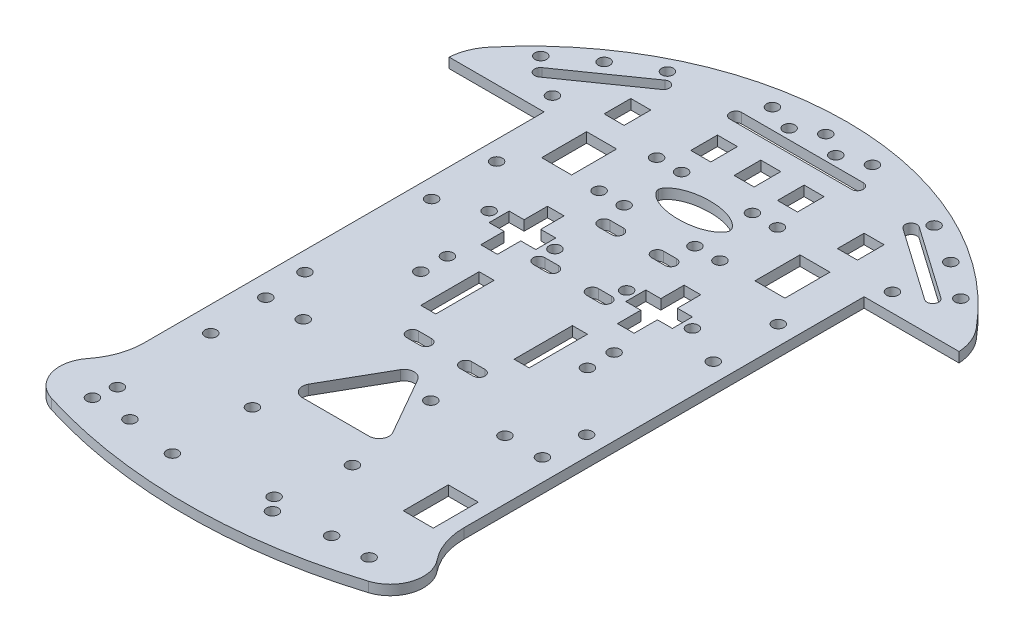
SolidWorks part; units mm, degrees
ref_plane "Front Plane" through (0, 0, 0) normal (0, 0, 1) x (1, 0, 0)
ref_plane "Top Plane" through (0, 0, 0) normal (0, 1, 0) x (1, 0, 0)
ref_plane "Right Plane" through (0, 0, 0) normal (1, 0, 0) x (0, 0, -1)
ref_plane "Plane4" through (0, -1.5, 0) normal (0, -1, 0) x (1, 0, 0)
sketch "Sketch1" plane through (0, -1.5, 0) normal (0, -1, 0) x (1, 0, 0)
  line L0 (6, 21.75) -> (10, 21.75)
  line L1 (10, 18.25) -> (6, 18.25)
  line L2 (-10, 41.25) -> (-6, 41.25)
  line L3 (-6, 37.75) -> (-10, 37.75)
  line L4 (6, 79.25) -> (10, 79.25)
  line L5 (10, 75.75) -> (6, 75.75)
  line L6 (-10, 110.5) -> (10, 110.5)
  line L7 (12.6047, 106.0116) -> (2.6047, 88.5116)
  line L8 (-2.6047, 88.5116) -> (-12.6047, 106.0116)
  line L9 (-57.85, -8.3165) -> (-36.1425, -23.5163)
  line L10 (-38.15, -26.3833) -> (-59.8575, -11.1835)
  line L11 (23, 44) -> (23, 37)
  line L12 (23, 37) -> (27.5, 37)
  line L13 (27.5, 37) -> (27.5, 31)
  line L14 (27.5, 31) -> (23, 31)
  line L15 (23, 31) -> (23, 24)
  line L16 (23, 24) -> (18, 24)
  line L17 (18, 24) -> (18, 31)
  line L18 (18, 31) -> (13.5, 31)
  line L19 (13.5, 31) -> (13.5, 37)
  line L20 (13.5, 37) -> (18, 37)
  line L21 (18, 37) -> (18, 44)
  line L22 (18, 44) -> (23, 44)
  line L23 (16.25, 51.25) -> (11.75, 51.25)
  line L24 (11.75, 51.25) -> (11.75, 68.75)
  line L25 (11.75, 68.75) -> (16.25, 68.75)
  line L26 (16.25, 68.75) -> (16.25, 51.25)
  line L27 (43.5, 111.25) -> (34.5, 111.25)
  line L28 (34.5, 111.25) -> (34.5, 124.75)
  line L29 (34.5, 124.75) -> (43.5, 124.75)
  line L30 (43.5, 124.75) -> (43.5, 111.25)
  line L31 (-27.5, -1.25) -> (-36.5, -1.25)
  line L32 (-36.5, -1.25) -> (-36.5, 12.25)
  line L33 (-36.5, 12.25) -> (-27.5, 12.25)
  line L34 (-27.5, 12.25) -> (-27.5, -1.25)
  line L35 (16, -20) -> (10, -20)
  line L36 (10, -20) -> (10, -12)
  line L37 (10, -12) -> (16, -12)
  line L38 (16, -12) -> (16, -20)
  line L39 (37.5, -16.5) -> (31.5, -16.5)
  line L40 (31.5, -16.5) -> (31.5, -8.5)
  line L41 (31.5, -8.5) -> (37.5, -8.5)
  line L42 (37.5, -8.5) -> (37.5, -16.5)
  line L43 (-48, 0) -> (-76.5, 0)
  line L44 (76.5, 0) -> (48, 0)
  line L45 (48, 0) -> (48, 120)
  line L46 (-48, 120) -> (-48, 0)
  line L47 (-32.5, -16.5) -> (-38.5, -16.5)
  line L48 (-38.5, -16.5) -> (-38.5, -8.5)
  line L49 (-38.5, -8.5) -> (-32.5, -8.5)
  line L50 (-32.5, -8.5) -> (-32.5, -16.5)
  line L51 (-10, -20) -> (-16, -20)
  line L52 (-16, -20) -> (-16, -12)
  line L53 (-16, -12) -> (-10, -12)
  line L54 (-10, -12) -> (-10, -20)
  line L55 (3, -20) -> (-3, -20)
  line L56 (-3, -20) -> (-3, -12)
  line L57 (-3, -12) -> (3, -12)
  line L58 (3, -12) -> (3, -20)
  line L59 (36.5, -1.25) -> (27.5, -1.25)
  line L60 (27.5, -1.25) -> (27.5, 12.25)
  line L61 (27.5, 12.25) -> (36.5, 12.25)
  line L62 (36.5, 12.25) -> (36.5, -1.25)
  line L63 (-11.75, 51.25) -> (-16.25, 51.25)
  line L64 (-16.25, 51.25) -> (-16.25, 68.75)
  line L65 (-16.25, 68.75) -> (-11.75, 68.75)
  line L66 (-11.75, 68.75) -> (-11.75, 51.25)
  line L67 (-18, 44) -> (-18, 37)
  line L68 (-18, 37) -> (-13.5, 37)
  line L69 (-13.5, 37) -> (-13.5, 31)
  line L70 (-13.5, 31) -> (-18, 31)
  line L71 (-18, 31) -> (-18, 24)
  line L72 (-18, 24) -> (-23, 24)
  line L73 (-23, 24) -> (-23, 31)
  line L74 (-23, 31) -> (-27.5, 31)
  line L75 (-27.5, 31) -> (-27.5, 37)
  line L76 (-27.5, 37) -> (-23, 37)
  line L77 (-23, 37) -> (-23, 44)
  line L78 (-23, 44) -> (-18, 44)
  line L79 (-18.25, -26) -> (18.25, -26)
  line L80 (18.25, -29.5) -> (-18.25, -29.5)
  line L81 (59.8575, -11.1835) -> (38.15, -26.3833)
  line L82 (36.1425, -23.5163) -> (57.85, -8.3165)
  line L83 (-10, 79.25) -> (-6, 79.25)
  line L84 (-6, 75.75) -> (-10, 75.75)
  line L85 (6, 41.25) -> (10, 41.25)
  line L86 (10, 37.75) -> (6, 37.75)
  line L87 (-10, 21.75) -> (-6, 21.75)
  line L88 (-6, 18.25) -> (-10, 18.25)
  arc A0 (10, 21.75) -> (10, 18.25) centre (10, 20) cw
  arc A1 (6, 18.25) -> (6, 21.75) centre (6, 20) cw
  arc A2 (-6, 41.25) -> (-6, 37.75) centre (-6, 39.5) cw
  arc A3 (-10, 37.75) -> (-10, 41.25) centre (-10, 39.5) cw
  arc A4 (10, 79.25) -> (10, 75.75) centre (10, 77.5) cw
  arc A5 (6, 75.75) -> (6, 79.25) centre (6, 77.5) cw
  arc A6 (10, 110.5) -> (12.6047, 106.0116) centre (10, 107.5) cw
  arc A7 (2.6047, 88.5116) -> (-2.6047, 88.5116) centre (0, 90) cw
  arc A8 (-12.6047, 106.0116) -> (-10, 110.5) centre (-10, 107.5) cw
  arc A9 (-36.1425, -23.5163) -> (-38.15, -26.3833) centre (-37.1462, -24.9498) cw
  arc A10 (-59.8575, -11.1835) -> (-57.85, -8.3165) centre (-58.8538, -9.75) cw
  arc A11 (-76.5, 0) -> (-73.0709, -8.5857) centre (-61.5334, 1) ccw
  arc A12 (-73.0709, -8.5857) -> (73.0709, -8.5857) centre (0, 52.1238) ccw
  arc A13 (73.0709, -8.5857) -> (76.5, 0) centre (61.5334, 1) ccw
  arc A14 (48, 120) -> (52.3755, 132.485) centre (68, 120) cw
  arc A15 (52.3755, 132.485) -> (47.5341, 148.276) centre (44.5633, 138.7275) ccw
  arc A16 (47.5341, 148.276) -> (-47.5341, 148.276) centre (0, -4.5) ccw
  arc A17 (-47.5341, 148.276) -> (-52.3755, 132.485) centre (-44.5633, 138.7275) ccw
  arc A18 (-52.3755, 132.485) -> (-48, 120) centre (-68, 120) cw
  arc A19 (18.25, -26) -> (18.25, -29.5) centre (18.25, -27.75) cw
  arc A20 (-18.25, -29.5) -> (-18.25, -26) centre (-18.25, -27.75) cw
  arc A21 (38.15, -26.3833) -> (36.1425, -23.5163) centre (37.1462, -24.9498) cw
  arc A22 (57.85, -8.3165) -> (59.8575, -11.1835) centre (58.8538, -9.75) cw
  arc A23 (-6, 79.25) -> (-6, 75.75) centre (-6, 77.5) cw
  arc A24 (-10, 75.75) -> (-10, 79.25) centre (-10, 77.5) cw
  arc A25 (10, 41.25) -> (10, 37.75) centre (10, 39.5) cw
  arc A26 (6, 37.75) -> (6, 41.25) centre (6, 39.5) cw
  arc A27 (-6, 21.75) -> (-6, 18.25) centre (-6, 20) cw
  arc A28 (-10, 18.25) -> (-10, 21.75) centre (-10, 20) cw
  circle A29 centre (-7, -32.5) radius 1.75
  circle A30 centre (0, -36.5) radius 1.75
  circle A31 centre (7, -32.5) radius 1.75
  circle A32 centre (15, -35.5) radius 1.75
  circle A33 centre (-15, -35.5) radius 1.75
  circle A34 centre (-40, -29) radius 1.75
  circle A35 centre (-52, -22) radius 1.75
  circle A36 centre (-63, -14) radius 1.75
  circle A37 centre (63, -14) radius 1.75
  circle A38 centre (52, -22) radius 1.75
  circle A39 centre (40, -29) radius 1.75
  circle A40 centre (-19.25, -5) radius 1.75
  circle A41 centre (-11.75, -5) radius 1.75
  circle A42 centre (-11.75, 12.25) radius 1.75
  circle A43 centre (-19.25, 12.25) radius 1.75
  circle A44 centre (9.5, 12.25) radius 1.75
  circle A45 centre (17, 12.25) radius 1.75
  circle A46 centre (17, -5) radius 1.75
  circle A47 centre (9.5, -5) radius 1.75
  circle A48 centre (-51, -5.5) radius 1.75
  circle A49 centre (-42.25, 20) radius 1.75
  circle A50 centre (42.25, 20) radius 1.75
  circle A51 centre (51, -5.5) radius 1.75
  circle A52 centre (-10.75, 34) radius 1.75
  circle A53 centre (-30.5, 34) radius 1.75
  circle A54 centre (10.75, 34) radius 1.75
  circle A55 centre (30.5, 34) radius 1.75
  circle A56 centre (42.25, 39.5) radius 1.75
  circle A57 centre (25, 52) radius 1.75
  circle A58 centre (25, 60) radius 1.75
  circle A59 centre (-25, 60) radius 1.75
  circle A60 centre (-25, 52) radius 1.75
  circle A61 centre (-42.25, 39.5) radius 1.75
  circle A62 centre (-42.25, 77.4983) radius 1.75
  circle A63 centre (-41.5, 90) radius 1.75
  circle A64 centre (-30.25, 90) radius 1.75
  circle A65 centre (-40.5, 107.5) radius 1.75
  circle A66 centre (-15, 120.5) radius 1.75
  circle A67 centre (-40.5, 135.5) radius 1.75
  circle A68 centre (-41.5, 142) radius 1.75
  circle A69 centre (-30.25, 142) radius 1.75
  circle A70 centre (-15, 144.5) radius 1.75
  circle A71 centre (11.5, 140.5) radius 1.75
  circle A72 centre (15, 144.5) radius 1.75
  circle A73 centre (30.25, 142) radius 1.75
  circle A74 centre (41.5, 142) radius 1.75
  circle A75 centre (15, 120.5) radius 1.75
  circle A76 centre (10, 92) radius 1.75
  circle A77 centre (30.25, 90) radius 1.75
  circle A78 centre (41.5, 90) radius 1.75
  circle A79 centre (42.25, 77.4983) radius 1.75
  spline S0 degree 3 poles (10.75, 3) (10.75, 4.5833) (7.1667, 7.75) (-7.1667, 7.75) (-10.75, 4.5833) (-10.75, 3) knots 0 0 0 0 0.5 0.5 1 1 1 1
  spline S1 degree 3 poles (-10.75, 3) (-10.75, 1.4167) (-7.1667, -1.75) (7.1667, -1.75) (10.75, 1.4167) (10.75, 3) knots 0 0 0 0 0.5 0.5 1 1 1 1
  dimension "D1" = 3.5
  dimension "D2" = 3.5
  dimension "D3" = 3.5
  dimension "D4" = 3.5
  dimension "D5" = 3.5
  dimension "D6" = 3.5
  dimension "D7" = 3.5
  dimension "D8" = 3.5
  dimension "D9" = 3.5
  dimension "D10" = 3.5
  dimension "D11" = 3.5
  dimension "D12" = 3.5
  dimension "D13" = 3.5
  dimension "D14" = 3.5
  dimension "D15" = 3.5
  dimension "D16" = 3.5
  dimension "D17" = 3.5
  dimension "D18" = 3.5
  dimension "D19" = 3.5
  dimension "D20" = 3.5
  dimension "D21" = 3.5
  dimension "D22" = 3.5
  dimension "D23" = 3.5
  dimension "D24" = 3.5
  dimension "D25" = 3.5
  dimension "D26" = 3.5
  dimension "D27" = 3.5
  dimension "D28" = 3.5
  dimension "D29" = 3.5
  dimension "D30" = 3.5
  dimension "D31" = 3.5
  dimension "D32" = 3.5
  dimension "D33" = 3.5
  dimension "D34" = 3.5
  dimension "D35" = 3.5
  dimension "D36" = 3.5
  dimension "D37" = 3.5
  dimension "D38" = 3.5
  dimension "D39" = 3.5
  dimension "D40" = 3.5
  dimension "D41" = 3.5
  dimension "D42" = 3.5
  dimension "D43" = 3.5
  dimension "D44" = 3.5
  dimension "D45" = 3.5
  dimension "D46" = 3.5
  dimension "D47" = 3.5
  dimension "D48" = 3.5
  dimension "D49" = 3.5
  dimension "D50" = 3.5
  dimension "D51" = 3.5
  dimension "D52" = 1.75
  dimension "D53" = 1.75
  dimension "D54" = 1.75
  dimension "D55" = 3
  dimension "D56" = 3
  dimension "D57" = 1.75
  dimension "D58" = 15
  dimension "D59" = 95
  dimension "D60" = 20
  dimension "D61" = 10
  dimension "D62" = 160
  dimension "D63" = 1.75
  dimension "D64" = 1.75
  dimension "D65" = 0.4659
  dimension "D66" = 3.4367
  dimension "D67" = 5.75
  dimension "D68" = 6.5
  dimension "D69" = 7.5
  dimension "D70" = 8
  dimension "D71" = 9.5
  dimension "D72" = 9.85
  dimension "D73" = 10.8538
  dimension "D74" = 11.5
  dimension "D75" = 11.8575
  dimension "D76" = 15.5
  dimension "D77" = 17.5
  dimension "D78" = 17.75
  dimension "D79" = 20.5
  dimension "D80" = 23
  dimension "D81" = 25
  dimension "D82" = 28.75
  dimension "D83" = 29.75
  dimension "D84" = 30
  dimension "D85" = 31.75
  dimension "D86" = 32
  dimension "D87" = 33
  dimension "D88" = 34.5
  dimension "D89" = 35.3953
  dimension "D90" = 36.25
  dimension "D91" = 37.25
  dimension "D92" = 38
  dimension "D93" = 41
  dimension "D94" = 42
  dimension "D95" = 45
  dimension "D96" = 84.1425
  dimension "D97" = 109.5334
  dimension "D98" = 124.5
  dimension "D99" = 51
  dimension "D100" = 54
  dimension "D101" = 55
  dimension "D102" = 57.5
  dimension "D103" = 9.85
  dimension "D104" = 58.75
  dimension "D105" = 59.5
  dimension "D106" = 59.75
  dimension "D107" = 0.5
  dimension "D108" = 61.5
  dimension "D109" = 63
  dimension "D110" = 64
  dimension "D111" = 64.25
  dimension "D112" = 65
  dimension "D113" = 66
  dimension "D114" = 66.25
  dimension "D115" = 71
  dimension "D116" = 73
  dimension "D117" = 75.5
  dimension "D118" = 78.25
  dimension "D119" = 78.5
  dimension "D120" = 79.5
  dimension "D121" = 82.5
  dimension "D122" = 3.1167
  dimension "D123" = 84.5
  dimension "D124" = 20.9143
  dimension "D125" = 85.5
  dimension "D126" = 25
  dimension "D127" = 88
  dimension "D128" = 89.5
  dimension "D129" = 90.25
  dimension "D130" = 91.5
  dimension "D131" = 7.5
  dimension "D132" = 9.5
  dimension "D133" = 13
  dimension "D134" = 99
  dimension "D135" = 100
  dimension "D136" = 15.5
  dimension "D137" = 17.5
  dimension "D138" = 118.0116
  dimension "D141" = 111
  dimension "D142" = 21
  dimension "D144" = 24
  dimension "D145" = 3
  dimension "D146" = 4
  dimension "D147" = 24.5
  dimension "D149" = 28.25
  dimension "D152" = 15
  dimension "D153" = 32.5
  dimension "D154" = 41.75
  dimension "D155" = 49.5
  dimension "D156" = 53.5
  dimension "D157" = 60.5
  dimension "D158" = 63.5
  dimension "D159" = 66.5
  dimension "D160" = 69
  dimension "D161" = 73.5
  dimension "D162" = 80.75
  dimension "D163" = 81.5
  dimension "D165" = 89.5
  dimension "D166" = 98.25
  dimension "D167" = 106.9983
  dimension "D168" = 107
  dimension "D171" = 121.5
  dimension "D175" = 140.75
  dimension "D177" = 150
  dimension "D178" = 154.25
  dimension "D180" = 165
  dimension "D182" = 170
  dimension "D183" = 171.5
  dimension "D184" = 174
  dimension "D186" = 3
  dimension "D187" = 6
  dimension "D188" = 7
extrude "Boss-Extrude1" add sketch "Sketch1" against normal blind 3
ref_axis "Axis1" through (0, 0, 173.8583) along (0, 0, -1)
